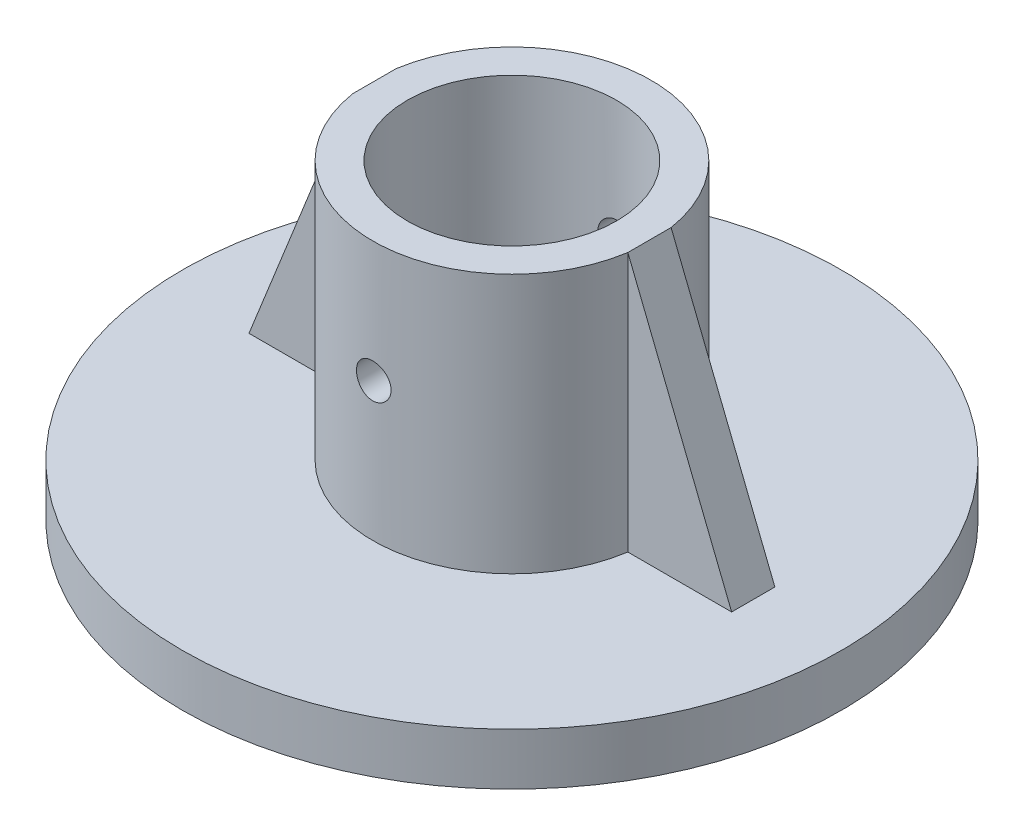
SolidWorks part; units mm, degrees
ref_plane "Ön Düzlem" through (0, 0, 0) normal (0, 0, 1) x (1, 0, 0)
ref_plane "Üst Düzlem" through (0, 0, 0) normal (0, 1, 0) x (1, 0, 0)
ref_plane "Sağ Düzlem" through (0, 0, 0) normal (1, 0, 0) x (0, 0, -1)
sketch "Çizim1" plane through (0, 0, 0) normal (0, 1, 0) x (1, 0, 0)
  line L0 (7.4934, 1.25) -> (13.9524, 1.25)
  line L1 (-13.9524, 1.25) -> (-7.3715, 1.25)
  line L2 (-13.9524, 1.25) -> (-13.9524, -1.25)
  line L3 (-13.9524, -1.25) -> (-7.3715, -1.25)
  line L4 (-7.3715, 1.25) -> (-7.3715, -1.25)
  line L5 (7.4934, 1.25) -> (7.4934, -1.25)
  line L6 (7.4934, -1.25) -> (13.9524, -1.25)
  line L7 (13.9524, 1.25) -> (13.9524, -1.25)
  line L8 (-7.3715, 3.2347) -> (-7.3715, -3.2347)
  line L9 (7.4934, 2.9413) -> (7.4934, -2.9413)
  line L10 (-7.9524, 1.25) -> (-7.9524, -1.25)
  line L11 (7.9524, 1.25) -> (7.9524, -1.25)
  circle A0 centre (0, 0) radius 6.05
  circle A1 centre (0, 0) radius 8.05
  circle A2 centre (0, 0) radius 19.0546
  point P11 (-7.3715, 0)
  point P19 (7.4934, 0)
  point P24 (-13.9524, 0)
  dimension "D1" = 12.1
  dimension "D5" = 6
  dimension "D3" = 6
  dimension "D4" = 2.5
  dimension "D6" = 2.5
  dimension "D2" = 2
extrude "Yükseklik-Ekstrüzyon1" add sketch "Çizim1" along normal blind 3 contours A2 A1 L0 L7 L6 L3 L2 L1 | A1 L6 L7 L0 | A1 L1 L2 L3 | L5 A1 L4 A0 | L8 A1 L1 | L1 L10 L3 L4 | L3 A1 L8 | L0 A1 L9 | L11 L0 L5 L6 | L9 A1 L6 | L10 A1 | L11 A1 | A0 region at (7.6584, 0, -1.8499) region at (7.7229, 0, 0) region at (7.2743, 0, 0) region at (7.9914, 0, 0) region at (10.9849, 0, 0) region at (7.6584, 0, 1.8499) region at (-7.582, 0, -1.9581) region at (-7.582, 0, 1.9581) region at (-7.6619, 0, 0) region at (-10.9849, 0, 0) region at (-7.9914, 0, 0) region at (0, 0, 0) region at (-18.5156, 0, 0)
extrude "Yükseklik-Ekstrüzyon2" add sketch "Çizim1<3>" along normal offset from surface (18 mm away) 15 contours A1 | A0 up to face at (0, 3, 19.0546) offset beyond the face yes
sketch "Çizim1<3>" plane through (0, 0, 0) normal (0, 1, 0) x (1, 0, 0) same geometry as "Çizim1"
extrude "Yükseklik-Ekstrüzyon10" add sketch "Çizim1<11>" along normal up to surface (18 mm away) contours A1 L1 L2 L3 | A1 L6 L7 L0 region at (10.9849, 0, 0) region at (-10.9849, 0, 0) up to face at (0, 18, 6.05)
sketch "Çizim1<11>" plane through (0, 0, 0) normal (0, 1, 0) x (1, 0, 0) same geometry as "Çizim1"
sketch "Çizim5" plane through (0, 0, 0) normal (0, 0, 1) x (1, 0, 0)
  line L0 (-13.9524, 3) -> (-7.9524, 18)
  line L1 (-7.9524, 18) -> (-13.9524, 18)
  line L2 (-13.9524, 18) -> (-13.9524, 3)
  line L3 (7.9524, 18) -> (13.9524, 18)
  line L4 (13.9524, 18) -> (13.9524, 3)
  line L5 (13.9524, 3) -> (7.9524, 18)
  line L6 (-13.9524, 18) -> (-7.9524, 18) construction
  line L7 (-7.9524, 18) -> (-7.9524, 3) construction
  line L8 (7.9524, 18) -> (13.9524, 18) construction
extrude "Kes-Ekstrüzyon1" cut sketch "Çizim5" against normal through all both and the other way through all contours L2 L0 L1 | L5 L3 L4
sketch "Çizim6" plane through (0, 0, 0) normal (0, 0, 1) x (1, 0, 0)
  line L0 (7.9524, 18) -> (-7.9524, 18) construction
  circle A0 centre (0, 11) radius 1
  dimension "D1" = 2
  dimension "D2" = 7
extrude "Kes-Ekstrüzyon2" cut sketch "Çizim6" against normal through all both and the other way through all
